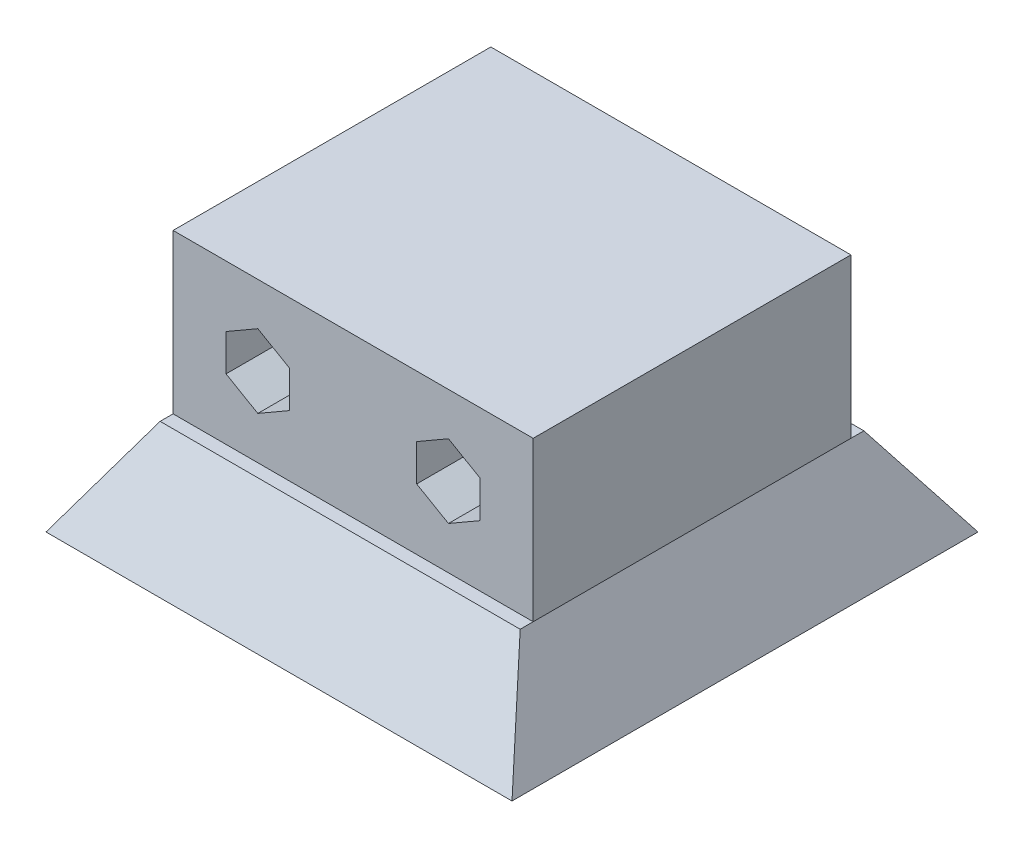
SolidWorks part; units mm, degrees
ref_plane "Front Plane" through (0, 0, 0) normal (0, 0, 1) x (1, 0, 0)
ref_plane "Top Plane" through (0, 0, 0) normal (0, 1, 0) x (1, 0, 0)
ref_plane "Right Plane" through (0, 0, 0) normal (1, 0, 0) x (0, 0, -1)
sketch "Sketch1" plane through (0, 0, 0) normal (0, 0, 1) x (1, 0, 0)
  line L1 (0, 0) -> (34, 0)
  line L2 (0, 0) -> (0, 15)
  line L3 (0, 15) -> (34, 15)
  line L4 (34, 0) -> (34, 15)
  dimension "D1" = 34
  dimension "D2" = 15
extrude "Boss-Extrude1" add sketch "Sketch1" along normal blind 30
sketch "Sketch3" plane through (0, 0, 30) normal (0, 0, 1) x (1, 0, 0)
  line L0 (0, 0) -> (-5, -8.6603)
  line L1 (-5, -8.6603) -> (39, -8.6603)
  line L2 (39, -8.6603) -> (34, 0)
  line L3 (0, 0) -> (34, 0) construction
  line L4 (0, 0) -> (34, 0)
  dimension "D1" = 120
  dimension "D2" = 120
  dimension "D3" = 44
extrude "Boss-Extrude2" add sketch "Sketch3" against normal blind 37 and the other way blind 7
sketch "Sketch4" plane through (0, 0, 0) normal (-0.866, 0.5, 0) x (0, 0, 1)
  line L0 (-7, -10) -> (-1.2265, 0)
  line L1 (0, 0) -> (-7, 0) construction
  line L2 (37, -10) -> (31.2265, 0)
  line L3 (37, 0) -> (30, 0) construction
  line L4 (-1.2265, 0) -> (-7, 0)
  line L5 (-7, 0) -> (-7, -10)
  line L6 (31.2265, 0) -> (37, 0)
  line L7 (37, 0) -> (37, -10)
  dimension "D1" = 120
  dimension "D2" = 120
extrude "Cut-Extrude1" cut sketch "Sketch4" along direction (1, 0, 0) on the side against the normal through all
sketch "Sketch5" plane through (0, 0, 30) normal (0, 0, 1) x (1, 0, 0)
  line L0 (34, 15) -> (0, 15) construction
  line L1 (8, 4.0359) -> (11, 5.7679)
  line L2 (11, 5.7679) -> (11, 9.2321)
  line L3 (11, 9.2321) -> (8, 10.9641)
  line L4 (8, 10.9641) -> (5, 9.2321)
  line L5 (5, 9.2321) -> (5, 5.7679)
  line L6 (5, 5.7679) -> (8, 4.0359)
  line L7 (26, 4.0359) -> (29, 5.7679)
  line L8 (29, 5.7679) -> (29, 9.2321)
  line L9 (29, 9.2321) -> (26, 10.9641)
  line L10 (26, 10.9641) -> (23, 9.2321)
  line L11 (23, 9.2321) -> (23, 5.7679)
  line L12 (23, 5.7679) -> (26, 4.0359)
  line L14 (0, 15) -> (0, 0) construction
  line L15 (34, 0) -> (34, 15) construction
  circle A0 centre (8, 7.5) radius 3 construction
  circle A1 centre (26, 7.5) radius 3 construction
  dimension "D1" = 7.5
  dimension "D2" = 7.5
  dimension "D3" = 8
  dimension "D4" = 6
  dimension "D5" = 6
  dimension "D6" = 8
extrude "Cut-Extrude2" cut sketch "Sketch5" against normal through all
